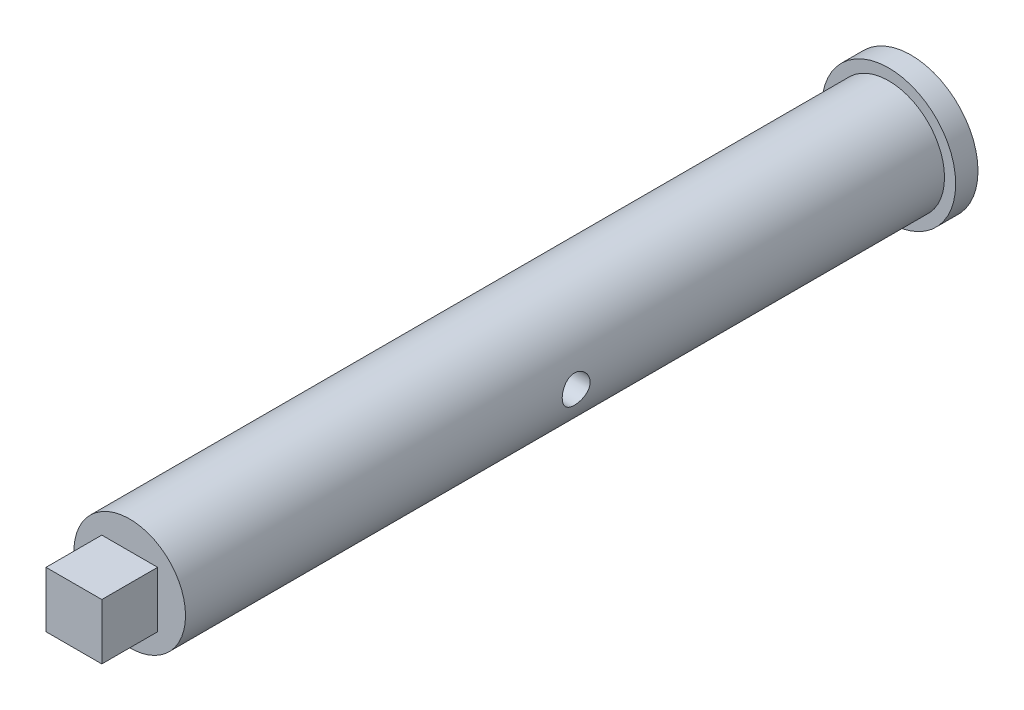
SolidWorks part; units mm, degrees
ref_plane "Plan de face" through (0, 0, 0) normal (0, 0, 1) x (1, 0, 0)
ref_plane "Plan de dessus" through (0, 0, 0) normal (0, 1, 0) x (1, 0, 0)
ref_plane "Plan de droite" through (0, 0, 0) normal (1, 0, 0) x (0, 0, -1)
sketch "Sketch6" plane through (0, 0, 0) normal (0, 0, 1) x (1, 0, 0)
  circle A0 centre (0, 0) radius 6
  dimension "D1" = 12
extrude "Boss-Extrude4" add sketch "Sketch6" along normal blind 2
sketch "Sketch1" plane through (0, 0, 2) normal (0, 0, 1) x (1, 0, 0)
  circle A0 centre (0, 0) radius 5
  dimension "D1" = 10
extrude "Boss-Extrude1" add sketch "Sketch1" along normal blind 68
sketch "Sketch2" plane through (0, 0, 70) normal (0, 0, 1) x (1, 0, 0)
  line L1 (-2.5, -2.5) -> (2.5, -2.5)
  line L2 (-2.5, -2.5) -> (-2.5, 2.5)
  line L3 (-2.5, 2.5) -> (2.5, 2.5)
  line L4 (2.5, -2.5) -> (2.5, 2.5)
  point P4 (2.5, 0)
  point P5 (0, 2.5)
  dimension "D1" = 5
  dimension "D2" = 5
extrude "Boss-Extrude2" add sketch "Sketch2" along normal blind 5
sketch "Sketch5" plane through (0, 0, 0) normal (1, 0, 0) x (0, 0, -1)
  line L0 (-70, 0) -> (-35, 0) construction
  line L1 (-70, 5) -> (-70, -5) construction
  circle A0 centre (-35, 0) radius 1.25
  dimension "D2" = 1.25
  dimension "D1" = 35
extrude "Cut-Extrude1" cut sketch "Sketch5" against normal blind 5 and the other way blind 5
